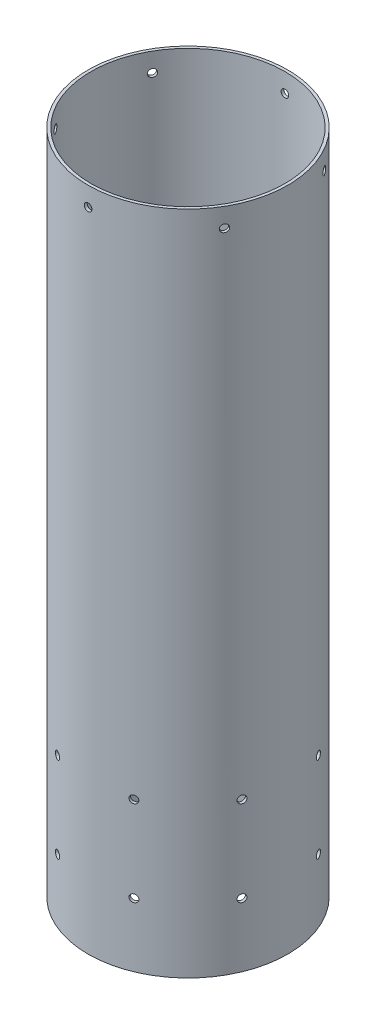
SolidWorks part; units mm, degrees
ref_plane "Спереди" through (0, 0, 0) normal (0, 0, 1) x (1, 0, 0)
ref_plane "Сверху" through (0, 0, 0) normal (0, 1, 0) x (1, 0, 0)
ref_plane "Справа" through (0, 0, 0) normal (1, 0, 0) x (0, 0, -1)
other "Configuration Table"
sketch "Эскиз1" plane through (0, 0, 0) normal (0, 1, 0) x (1, 0, 0)
  circle A0 centre (0, 0) radius 52.5
  circle A1 centre (0, 0) radius 51
  dimension "D1" = 105
  dimension "D2" = 102
extrude "Бобышка-Вытянуть1" add sketch "Эскиз1" along normal blind 350
sketch "Эскиз2" plane through (0, 0, 0) normal (0, 0, 1) x (1, 0, 0)
  line L0 (0, -1000) -> (0, 342) construction
  line L1 (52.5, 350) -> (-52.5, 350) construction
  line L2 (51, 350) -> (-51, 350) construction
  circle A0 centre (0, 340) radius 2
  point P7 (0, 350)
  dimension "D1" = 4
  dimension "D2" = 10
extrude "Вырез-Вытянуть1" cut sketch "Эскиз2" along normal blind 64
pattern_circular "Круговой массив1" count 6 over 360 about axis through (0, 350, 0) along (0, -1, 0) of "Вырез-Вытянуть1"
sketch "Эскиз3" plane through (0, 0, 0) normal (0, 1, 0) x (1, 0, 0)
  line L0 (0, 0) -> (52.5, 0) construction
  line L2 (0, 0) -> (36.0624, -36.0624) construction
  circle A0 centre (0, 0) radius 51 construction
  circle A1 centre (0, 0) radius 52.5 construction
  point P5 (36.0624, -36.0624)
  point P6 (52.5, 0)
  dimension "D1" = 45
ref_plane "Плоскость1" through (0, 0, 0) normal (0.7071, 0, 0.7071) x (0, 1, 0)
sketch "Эскиз4" plane through (0, 0, 0) normal (0, 0, 1) x (1, 0, 0)
  line L0 (0, 0) -> (0, 350) construction
  line L1 (51, 350) -> (-51, 350) construction
  circle A0 centre (0, 35) radius 2
  circle A1 centre (0, 80) radius 2
  dimension "D2" = 4
  dimension "D3" = 4
  dimension "D1" = 35
  dimension "D4" = 45
sketch "Эскиз5" plane through (0, 0, 0) normal (0, 1, 0) x (1, 0, 0)
  line L0 (0, 0) -> (0, -51) construction
  line L1 (0, -51) -> (36.0624, -36.0624) construction
  line L2 (36.0624, -36.0624) -> (0, 0) construction
  line L3 (0, 0) -> (51, 0) construction
  line L4 (0, 0) -> (21.5535, -46.2217) construction
  line L5 (21.5535, -46.2217) -> (0, -51) construction
  circle A0 centre (0, 0) radius 51 construction
  dimension "D1" = 45
  dimension "D2" = 25
ref_plane "Плоскость2" through (18.0312, 0, 43.5312) normal (0.3827, 0, 0.9239) x (0.9239, 0, -0.3827)
sketch "Эскиз6" plane through (18.0312, 0, 43.5312) normal (0.3827, 0, 0.9239) x (0.9239, 0, -0.3827)
  line L0 (0, 0) -> (0, 350) construction
  circle A0 centre (0, 33.5) radius 2
  circle A1 centre (0, 78.5) radius 2
  dimension "D1" = 4
  dimension "D2" = 33.5
  dimension "D3" = 4
  dimension "D4" = 45
extrude "Вырез-Вытянуть3" cut sketch "Эскиз6" against normal blind 140
pattern_circular "Круговой массив2" count 8 over 360 about axis through (0, 350, 0) along (0, -1, 0) of "Вырез-Вытянуть3" reverse direction yes
